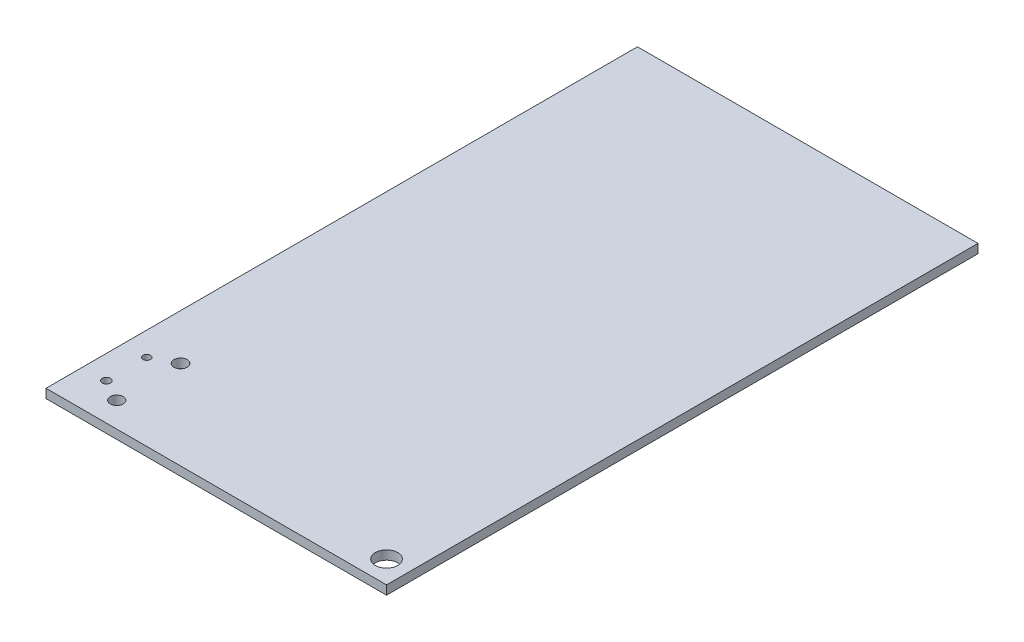
SolidWorks part; units mm, degrees
ref_plane "Front Plane" through (0, 0, 0) normal (0, 0, 1) x (1, 0, 0)
ref_plane "Top Plane" through (0, 0, 0) normal (0, 1, 0) x (1, 0, 0)
ref_plane "Right Plane" through (0, 0, 0) normal (1, 0, 0) x (0, 0, -1)
sketch "Sketch1" plane through (0, 0, 0) normal (0, 1, 0) x (1, 0, 0)
  line L1 (0, 0) -> (38, 0)
  line L2 (0, 0) -> (0, 66)
  line L3 (0, 66) -> (38, 66)
  line L4 (38, 0) -> (38, 66)
  dimension "D1" = 38
  dimension "D2" = 66
extrude "Boss-Extrude1" add sketch "Sketch1" along normal blind 1
sketch "Sketch2" plane through (0, 1, 0) normal (0, 1, 0) x (1, 0, 0)
  line L0 (0, 0) -> (38, 0) construction
  line L1 (38, 0) -> (38, 66) construction
  circle A0 centre (35.5, 2.5) radius 1.25
  dimension "D3" = 2.5
  dimension "D1" = 2.5
  dimension "D2" = 2.5
extrude "Cut-Extrude1" cut sketch "Sketch2" against normal through all
sketch "Sketch3" plane through (0, 1, 0) normal (0, 1, 0) x (1, 0, 0)
  circle A0 centre (2.638, 4.0988) radius 0.4568
  circle A1 centre (2.638, 8.6133) radius 0.41
  circle A2 centre (5.1076, 9.91) radius 0.7399
  circle A3 centre (5.1076, 2.7852) radius 0.7163
  point P8 (2.638, 8.6133)
extrude "Cut-Extrude2" cut sketch "Sketch3" against normal through all
